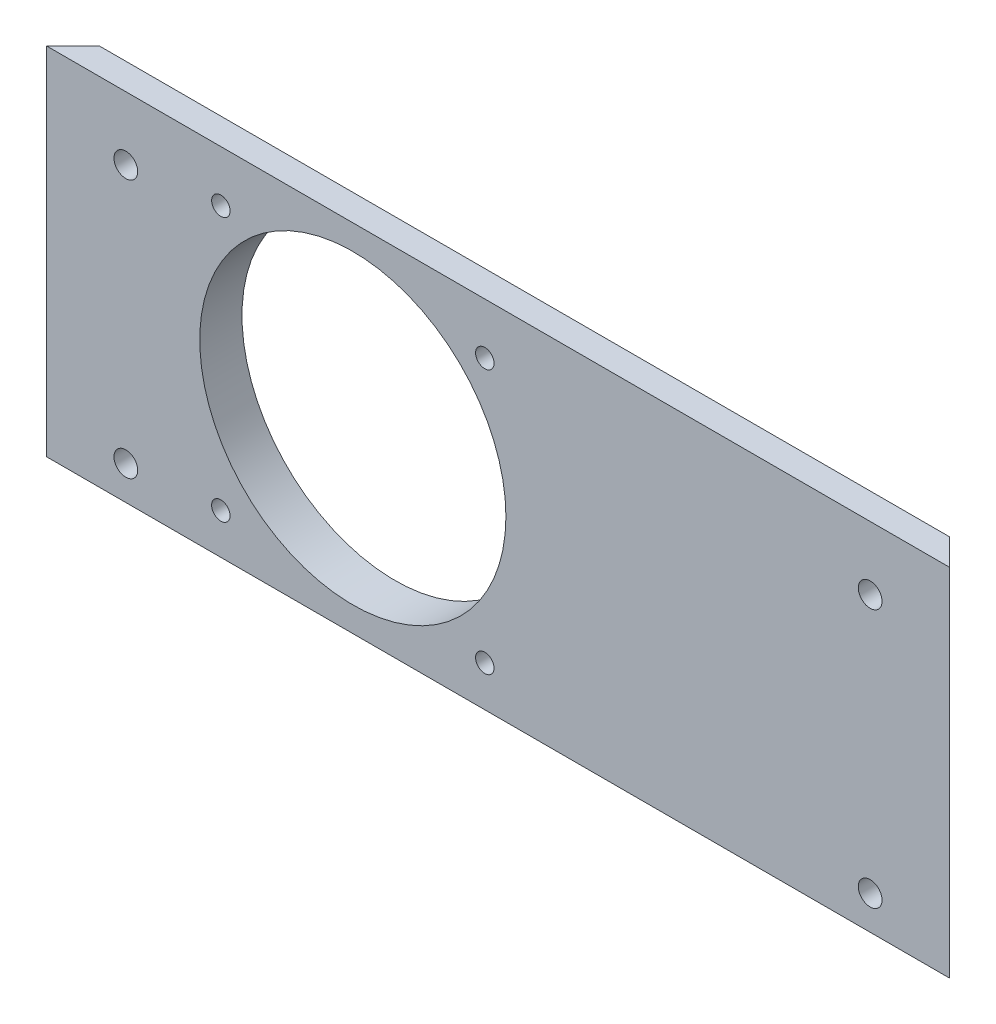
SolidWorks part; units mm, degrees
ref_plane "Front Plane" through (0, 0, 0) normal (0, 0, 1) x (1, 0, 0)
ref_plane "Top Plane" through (0, 0, 0) normal (0, 1, 0) x (1, 0, 0)
ref_plane "Right Plane" through (0, 0, 0) normal (1, 0, 0) x (0, 0, -1)
sketch "Sketch1" plane through (0, 0, 0) normal (0, 0, 1) x (1, 0, 0)
  line L0 (85.5, 70) -> (85.5, -37.3998) construction
  line L1 (0, 0) -> (171, 0)
  line L2 (0, 0) -> (0, 70)
  line L3 (0, 70) -> (171, 70)
  line L4 (171, 0) -> (171, 70)
  line L5 (0, 35) -> (171, 35) construction
  circle A0 centre (15, 9) radius 2.25
  circle A1 centre (156, 9) radius 2.25
  circle A4 centre (15, 58) radius 2.25
  circle A5 centre (156, 58) radius 2.25
  dimension "D3" = 15
  dimension "D5" = 4.5
  dimension "D1" = 70
  dimension "D2" = 171
  dimension "D4" = 9
  dimension "D6" = 2
  dimension "D7" = 12
extrude "Boss-Extrude1" add sketch "Sketch1" against normal blind 5
sketch "Sketch2" plane through (0, 0, -5) normal (0, 0, -1) x (-1, 0, 0)
  line L0 (0, 0) -> (-171, 0) construction
  line L1 (0, 0) -> (-171, 0) construction
  line L2 (0, 5) -> (-171, 5)
  line L3 (-171, 5) -> (-171, 70)
  line L4 (-171, 70) -> (0, 70)
  line L5 (0, 70) -> (0, 5)
  circle A1 centre (-15, 9) radius 2.25 construction
  circle A2 centre (-156, 9) radius 2.25 construction
  circle A5 centre (-15, 9) radius 2.25
  circle A6 centre (-156, 9) radius 2.25
  circle A8 centre (-15, 58) radius 2.25 construction
  circle A9 centre (-156, 58) radius 2.25 construction
  circle A10 centre (-15, 58) radius 2.25
  circle A11 centre (-156, 58) radius 2.25
  dimension "D1" = 5
extrude "Boss-Extrude2" add sketch "Sketch2" along normal blind 3
chamfer "Chamfer1" distance 8 angle 45 3 edges at (171, 37.5, -8) (0, 37.5, -8) (85.5, 70, -8)
chamfer "Chamfer3" distance 3 angle 45 1 edges at (85.5, 70, -8)
sketch "Sketch3" plane through (85.5, 0, -85.5) normal (0.7071, 0, -0.7071) x (-0.7071, 0, -0.7071)
  line L0 (-120.9153, 0) -> (-120.9153, 2.6)
  line L1 (-120.9153, 0) -> (-120.9153, 70) construction
  line L2 (-120.9153, 2.6) -> (-113.8442, 2.6)
  line L4 (-113.8442, 2.6) -> (-113.8442, 0)
  line L5 (-113.8442, 0) -> (-120.9153, 0)
  line L6 (-109.6016, 5) -> (-113.8442, 5) construction
  dimension "D1" = 2.4
extrude "Cut-Extrude1" cut sketch "Sketch3" along direction (1, 0, 0) on the side against the normal through all
sketch "Sketch4" plane through (0, 0, 0) normal (0, 0, 1) x (1, 0, 0)
  line L0 (171, 70) -> (0, 70) construction
  line L1 (93, 26) -> (141, 26) construction
  line L2 (93, 26) -> (93, 55) construction
  line L3 (93, 55) -> (141, 55) construction
  line L4 (141, 26) -> (141, 55) construction
  line L5 (171, 2.6) -> (171, 70) construction
  line L6 (111, 59.75) -> (111, 21.25) construction
  line L7 (93, 40.5) -> (141, 40.5) construction
  line L8 (29, 36.3) -> (28, 36.3) construction
  line L9 (28, 36.3) -> (28, 65.3) construction
  line L10 (28, 65.3) -> (58, 65.3) construction
  line L11 (28, 60.3) -> (33, 60.3) construction
  line L12 (33, 60.3) -> (33, 65.3) construction
  circle A0 centre (58, 36.3) radius 29
  circle A1 centre (33, 60.3) radius 1.75
  circle A2 centre (83, 60.3) radius 1.75
  circle A3 centre (83, 10.3) radius 1.75
  circle A4 centre (33, 10.3) radius 1.75
  circle A5 centre (111, 59.75) radius 1.75 construction
  circle A6 centre (111, 21.25) radius 1.75 construction
  point P28 (111, 40.5)
  point P31 (0, 0)
  dimension "D5" = 58
  dimension "D6" = 33.7
  dimension "D8" = 5
  dimension "D11" = 3.5
  dimension "D1" = 29
  dimension "D2" = 48
  dimension "D3" = 15
  dimension "D4" = 30
  dimension "D7" = 35
  dimension "D9" = 5
  dimension "D10" = 1
  dimension "D14" = 38.5
  dimension "D15" = 0
  dimension "D12" = 2
  dimension "D13" = 2
extrude "Cut-Extrude2" cut sketch "Sketch4" against normal through all
